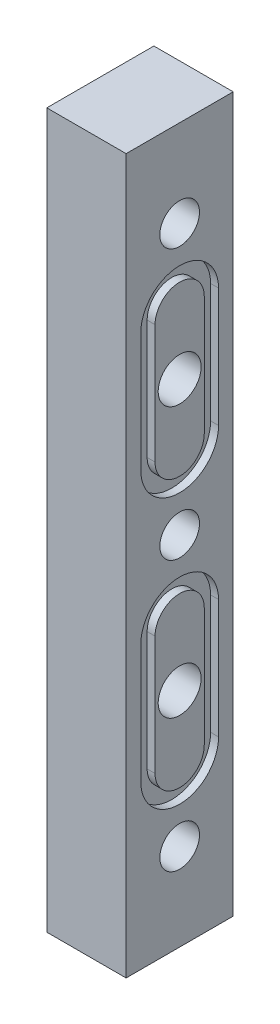
SolidWorks part; units mm, degrees
ref_plane "Front Plane" through (0, 0, 0) normal (0, 0, 1) x (1, 0, 0)
ref_plane "Top Plane" through (0, 0, 0) normal (0, 1, 0) x (1, 0, 0)
ref_plane "Right Plane" through (0, 0, 0) normal (1, 0, 0) x (0, 0, -1)
sketch "Sketch1" plane through (0, 0, 0) normal (1, 0, 0) x (0, 0, -1)
  line L1 (-4.7849, 53.6278) -> (8.7151, 53.6278)
  line L2 (-4.7849, 53.6278) -> (-4.7849, -36.3722)
  line L3 (-4.7849, -36.3722) -> (8.7151, -36.3722)
  line L4 (8.7151, 53.6278) -> (8.7151, -36.3722)
  dimension "D1" = 90
  dimension "D2" = 13.5
extrude "Boss-Extrude1" add sketch "Sketch1" along normal blind 10
hole_wizard "1/4-28 Tapped Hole1" positions "Sketch3" profile "Sketch2" tap size "1/4-28" standard "Ansi Inch" end condition through all
sketch "Sketch3" plane through (10, 0, 0) normal (1, 0, 0) x (0, 0, -1)
  line L0 (1.9651, 53.6278) -> (1.9651, -36.3722) construction
  line L1 (8.7151, 53.6278) -> (-4.7849, 53.6278) construction
  line L2 (-4.7849, -36.3722) -> (8.7151, -36.3722) construction
  line L3 (-4.7849, 53.6278) -> (-4.7849, -36.3722) construction
  point P0 (1.9651, 25.6278)
  point P1 (1.9651, -8.3722)
  point P8 (-4.7849, 8.6278)
  dimension "D1" = 17
  dimension "D2" = 34
sketch "Sketch2" plane through (10, 25.6278, -1.9651) normal (0, 1, 0) x (0, 0, -1)
  line L0 (0, 0) -> (0, 10)
  line L1 (0, 10) -> (2.7051, 10)
  line L2 (2.7051, 10) -> (2.7051, 0)
  line L5 (2.7051, 0) -> (0, 0)
  line L11 (0, -6.35) -> (0, 107.95) construction
  dimension "Thru Tap Drill Dia." = 5.4102
  dimension "Thru Tap Drill Depth" = 10
cosmetic thread "Hole Thread1" parameters "D1"=10, "D2"=6.35
cosmetic thread "Hole Thread2" parameters "D1"=10, "D2"=6.35
hole_wizard "Ø5.0 (5) Diameter Hole1" positions "Sketch5" profile "Sketch4" hole size "Ø5.0" standard "Ansi Metric"
sketch "Sketch5" plane through (10, 0, 0) normal (1, 0, 0) x (0, 0, -1)
  line L0 (1.9651, 53.6278) -> (1.9651, -36.3722) construction
  line L1 (8.7151, 53.6278) -> (-4.7849, 53.6278) construction
  line L2 (-4.7849, -36.3722) -> (8.7151, -36.3722) construction
  line L5 (1.9651, 42.6278) -> (1.9651, -25.3722) construction
  circle A0 centre (1.9651, 25.6278) radius 2.7051 construction
  circle A1 centre (1.9651, -8.3722) radius 2.7051 construction
  point P0 (1.9651, 42.6278)
  point P1 (1.9651, -25.3722)
  point P27 (1.9651, 8.6278)
  dimension "D1" = 17
  dimension "D2" = 17
sketch "Sketch4" plane through (10, 42.6278, -1.9651) normal (0, 1, 0) x (0, 0, -1)
  line L0 (0, 0) -> (0, 51.0022)
  line L1 (0, 51.0022) -> (2.5, 49.5)
  line L2 (2.5, 49.5) -> (2.5, 0)
  line L5 (2.5, 0) -> (0, 0)
  line L10 (0, 51.0022) -> (-2.5, 49.5) construction
  line L11 (0, -6.35) -> (0, 107.95) construction
  dimension "Hole Dia." = 5
  dimension "Hole Depth" = 49.5
  dimension "Drill Angle" = 118
sketch "Sketch6" plane through (10, 0, 0) normal (1, 0, 0) x (0, 0, -1)
  line L0 (1.9651, 33.1278) -> (1.9651, 18.1278) construction
  line L1 (5.0651, 33.1278) -> (5.0651, 18.1278)
  line L2 (-1.1349, 33.1278) -> (-1.1349, 18.1278)
  line L3 (1.9651, -0.8722) -> (1.9651, -15.8722) construction
  line L4 (5.0651, -0.8722) -> (5.0651, -15.8722)
  line L5 (-1.1349, -0.8722) -> (-1.1349, -15.8722)
  line L6 (1.9651, 33.1278) -> (1.9651, 18.1278) construction
  line L7 (6.8651, 33.1278) -> (6.8651, 18.1278)
  line L8 (-2.9349, 33.1278) -> (-2.9349, 18.1278)
  line L9 (1.9651, -0.8722) -> (1.9651, -15.8722) construction
  line L10 (6.8651, -0.8722) -> (6.8651, -15.8722)
  line L11 (-2.9349, -0.8722) -> (-2.9349, -15.8722)
  arc A0 (5.0651, 33.1278) -> (-1.1349, 33.1278) centre (1.9651, 33.1278) ccw
  arc A1 (-1.1349, 18.1278) -> (5.0651, 18.1278) centre (1.9651, 18.1278) ccw
  arc A2 (5.0651, -0.8722) -> (-1.1349, -0.8722) centre (1.9651, -0.8722) ccw
  arc A3 (-1.1349, -15.8722) -> (5.0651, -15.8722) centre (1.9651, -15.8722) ccw
  arc A4 (6.8651, 33.1278) -> (-2.9349, 33.1278) centre (1.9651, 33.1278) ccw
  arc A5 (-2.9349, 18.1278) -> (6.8651, 18.1278) centre (1.9651, 18.1278) ccw
  arc A6 (6.8651, -0.8722) -> (-2.9349, -0.8722) centre (1.9651, -0.8722) ccw
  arc A7 (-2.9349, -15.8722) -> (6.8651, -15.8722) centre (1.9651, -15.8722) ccw
  point P2 (1.9651, 25.6278)
  point P7 (1.9651, -8.3722)
  point P18 (1.9651, 25.6278)
  point P23 (1.9651, -8.3722)
  dimension "D1" = 6.2
  dimension "D2" = 15
  dimension "D3" = 1.8
  dimension "D4" = 15
extrude "Cut-Extrude1" cut sketch "Sketch6" against normal blind 1
sketch "Sketch7" plane through (0, 0, 0) normal (-1, 0, 0) x (0, 0, 1)
  line L1 (2.0099, 40.3329) -> (2.0099, 44.9228)
  line L2 (2.0099, 44.9228) -> (-1.9651, 47.2178)
  line L3 (-1.9651, 47.2178) -> (-5.9401, 44.9228)
  line L4 (-5.9401, 44.9228) -> (-5.9401, 40.3329)
  line L5 (-5.9401, 40.3329) -> (-1.9651, 38.0379)
  line L6 (-1.9651, 38.0379) -> (2.0099, 40.3329)
  line L7 (2.0099, 6.3329) -> (2.0099, 10.9228)
  line L8 (2.0099, 10.9228) -> (-1.9651, 13.2178)
  line L9 (-1.9651, 13.2178) -> (-5.9401, 10.9228)
  line L10 (-5.9401, 10.9228) -> (-5.9401, 6.3329)
  line L11 (-5.9401, 6.3329) -> (-1.9651, 4.0379)
  line L12 (-1.9651, 4.0379) -> (2.0099, 6.3329)
  line L13 (2.0099, -27.6671) -> (2.0099, -23.0772)
  line L14 (2.0099, -23.0772) -> (-1.9651, -20.7822)
  line L15 (-1.9651, -20.7822) -> (-5.9401, -23.0772)
  line L16 (-5.9401, -23.0772) -> (-5.9401, -27.6671)
  line L17 (-5.9401, -27.6671) -> (-1.9651, -29.9621)
  line L18 (-1.9651, -29.9621) -> (2.0099, -27.6671)
  circle A0 centre (-1.9651, 42.6278) radius 3.975 construction
  circle A1 centre (-1.9651, 8.6278) radius 3.975 construction
  circle A2 centre (-1.9651, -25.3722) radius 3.975 construction
  dimension "D1" = 7.95
extrude "Cut-Extrude2" cut sketch "Sketch7" against normal blind 5
